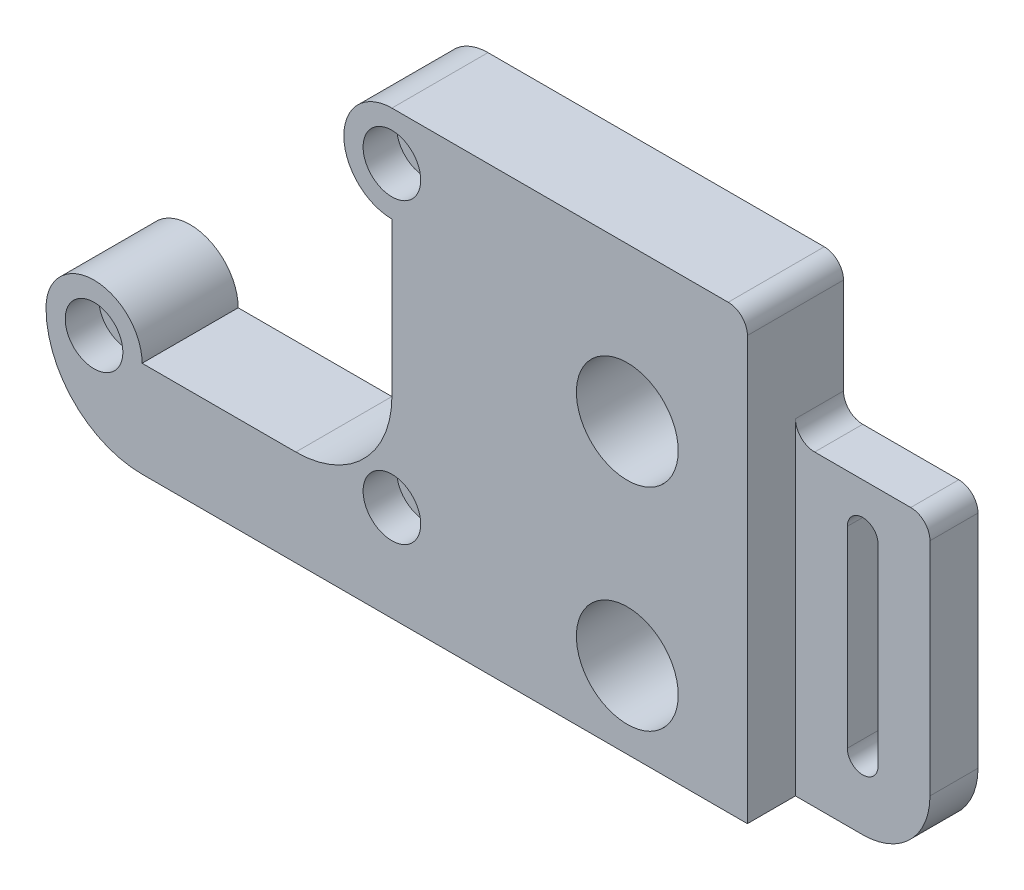
SolidWorks part; units mm, degrees
ref_plane "Front Plane" through (0, 0, 0) normal (0, 0, 1) x (1, 0, 0)
ref_plane "Top Plane" through (0, 0, 0) normal (0, 1, 0) x (1, 0, 0)
ref_plane "Right Plane" through (0, 0, 0) normal (1, 0, 0) x (0, 0, -1)
sketch "Sketch1" plane through (0, 0, 0) normal (0, 0, 1) x (1, 0, 0)
  line L0 (0, -5) -> (0, 5) construction
  line L1 (0, 5) -> (35, 5)
  line L2 (-26, -41) -> (44, -41)
  line L3 (51, -11) -> (51, -34)
  line L4 (44, -34) -> (44, -14) construction
  line L5 (42.4, -34) -> (42.4, -14)
  line L6 (45.6, -34) -> (45.6, -14)
  line L7 (49, -9) -> (39, -9)
  line L8 (19.2, -33) -> (29.8, -33) construction
  line L9 (24.5, -11) -> (24.5, -33) construction
  line L10 (0, -5) -> (0, -21)
  line L11 (-10, -31) -> (0, -31) construction
  line L12 (-31, -31) -> (-26, -31) construction
  line L13 (37, -7) -> (37, 3)
  line L14 (-10, -31) -> (-26, -31)
  line L15 (0, -31) -> (0, -21) construction
  line L16 (24.5, -33) -> (24.5, -41) construction
  line L17 (-31, -31) -> (-36, -31) construction
  arc A0 (0, 5) -> (0, -5) centre (0, 0) ccw
  circle A1 centre (0, 0) radius 1.8
  arc A2 (51, -11) -> (49, -9) centre (49, -11) ccw
  arc A3 (51, -34) -> (44, -41) centre (44, -34) cw
  arc A4 (42.4, -34) -> (45.6, -34) centre (44, -34) ccw
  circle A5 centre (24.5, -33) radius 5.3
  circle A6 centre (24.5, -11) radius 5.3
  circle A7 centre (0, -31) radius 1.8
  arc A8 (-26, -31) -> (-36, -31) centre (-31, -31) ccw
  circle A9 centre (-31, -31) radius 1.8
  arc A10 (45.6, -14) -> (42.4, -14) centre (44, -14) ccw
  arc A11 (-10, -31) -> (0, -21) centre (-10, -21) ccw
  arc A12 (-36, -31) -> (-26, -41) centre (-26, -31) ccw
  arc A13 (39, -9) -> (37, -7) centre (39, -7) cw
  arc A14 (35, 5) -> (37, 3) centre (35, 3) cw
  point P6 (44, -24)
  dimension "D1" = 10
  dimension "D2" = 3.6
  dimension "D4" = 14
  dimension "D8" = 10.6
  dimension "D9" = 22
  dimension "D10" = 31
  dimension "D12" = 20
  dimension "D13" = 2
  dimension "D7" = 2
  dimension "D11" = 7
  dimension "D5" = 10
  dimension "D14" = 70
  dimension "D6" = 3.2
  dimension "D3" = 24.5
  dimension "D15" = 14
extrude "Boss-Extrude1" add sketch "Sketch1" along normal blind 10 contours A11 L14 A8 L1 A0 L10 A9 A7 A6 A5 A4 A1 region at (15.8192, -21.3485, 0)
sketch "Sketch2" plane through (0, 0, 10) normal (0, 0, 1) x (1, 0, 0)
  circle A0 centre (-31, -31) radius 3
  circle A1 centre (0, -31) radius 3
  circle A2 centre (0, 0) radius 3
  dimension "D1" = 6
extrude "Cut-Extrude1" cut sketch "Sketch2" against normal blind 3.5
sketch "Sketch3" plane through (0, 0, 10) normal (0, 0, 1) x (1, 0, 0)
  line L0 (37, -41) -> (37, 5)
  line L1 (-26, -41) -> (44, -41) construction
  line L2 (0, 5) -> (35, 5) construction
  line L3 (37, -41) -> (44, -41)
  line L4 (37, 5) -> (51, 5)
  line L5 (51, 5) -> (51, -34)
  arc A0 (44, -41) -> (51, -34) centre (44, -34) ccw
  arc M6 (45.6, -34) -> (42.4, -34) centre (44, -34) cw
  line M12 (-26, -41) -> (44, -41)
  arc M13 (44, -41) -> (51, -34) centre (44, -34) ccw
  line M14 (51, -34) -> (51, -11)
  line M16 (35, 5) -> (0, 5)
  arc M35 (37, 3) -> (35, 5) centre (35, 3) ccw
  arc M36 (51, -11) -> (49, -9) centre (49, -11) ccw
  line M37 (49, -9) -> (39, -9)
  arc M38 (39, -9) -> (37, -7) centre (39, -7) cw
  line M39 (37, -7) -> (37, 3)
  arc M40 (42.4, -14) -> (45.6, -14) centre (44, -14) cw
  line M41 (45.6, -14) -> (45.6, -34)
  line M42 (42.4, -34) -> (42.4, -14)
extrude "Cut-Extrude2" cut sketch "Sketch3" against normal blind 5 contours L0 M12 M13 M14 M36 M37 M38 M39 M35 M16 M42 M40 M41 M6 | L5 L4 M35 M39 M38 M37 M36
